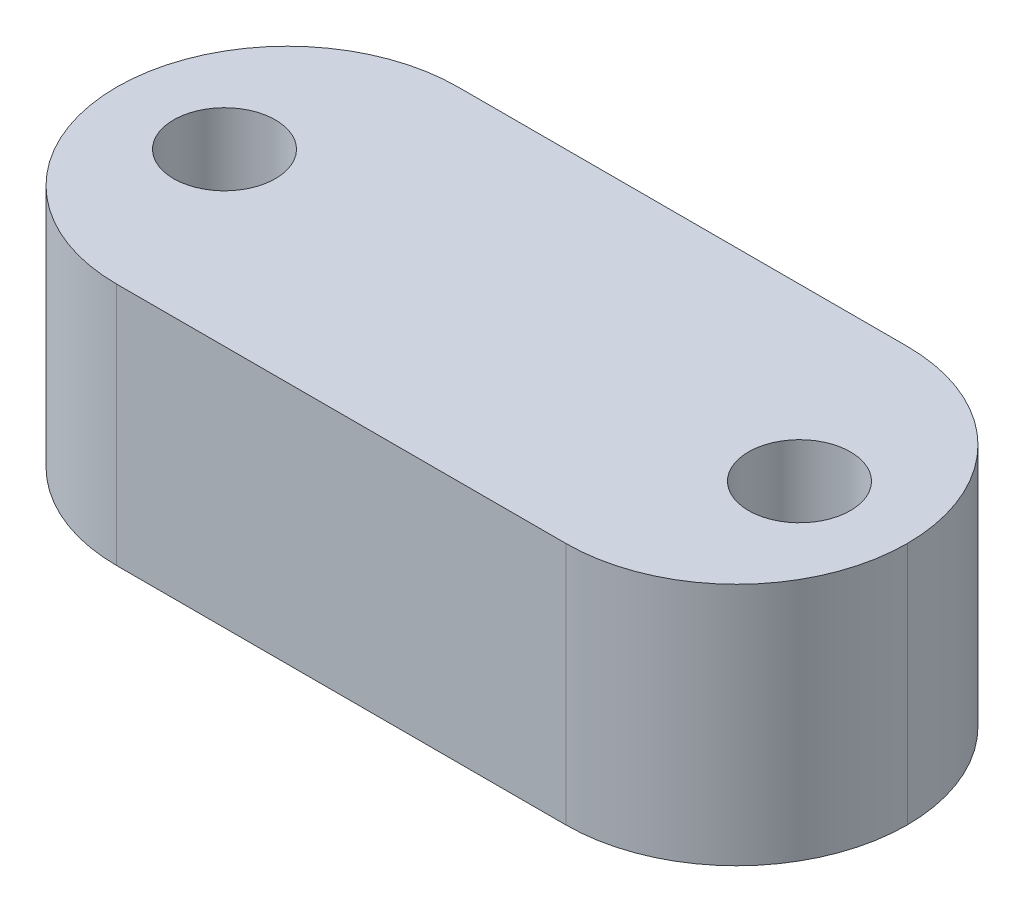
SolidWorks part; units mm, degrees
ref_plane "Front" through (0, 0, 0) normal (0, 0, 1) x (1, 0, 0)
ref_plane "Top" through (0, 0, 0) normal (0, 1, 0) x (1, 0, 0)
ref_plane "Right" through (0, 0, 0) normal (1, 0, 0) x (0, 0, -1)
sketch "Sketch1" plane through (0, 0, 0) normal (0, 1, 0) x (1, 0, 0)
  line L0 (0, 7.5406) -> (0, -7.5406) construction
  line L1 (-17.4625, 7.5406) -> (17.4625, 7.5406)
  line L2 (-17.4625, 7.5406) -> (-17.4625, -7.5406)
  line L3 (-17.4625, -7.5406) -> (17.4625, -7.5406)
  line L4 (17.4625, 7.5406) -> (17.4625, -7.5406)
  dimension "D1" = 15.0812
  dimension "D2" = 34.925
extrude "Extrude1" add sketch "Sketch1" along normal blind 10.7696
hole_wizard "M4 Clearance Hole1" positions "Sketch4" profile "Sketch3" hole size "M4" standard "Ansi Metric" end condition through all
sketch "Sketch4" plane through (0, 10.7696, 0) normal (0, 1, 0) x (-1, 0, 0)
  line L0 (12.7, 0) -> (-12.7, 0) construction
  point P0 (12.7, 0)
  point P1 (-12.7, 0)
  dimension "D1" = 25.4
sketch "Sketch3" plane through (-12.7, 10.7696, 0) normal (1, 0, 0) x (0, 0, 1)
  line L0 (0, 0) -> (0, 10.7696)
  line L1 (0, 10.7696) -> (2.25, 10.7696)
  line L2 (2.25, 10.7696) -> (2.25, 0)
  line L5 (2.25, 0) -> (0, 0)
  line L11 (0, -6.35) -> (0, 107.95) construction
  dimension "Thru Hole Dia." = 4.5
  dimension "Thru Hole Depth" = 10.7696
fillet "Fillet1" radius 7.5406 4 edges at (17.4625, 5.3848, 7.5406) (17.4625, 5.3848, -7.5406) (-17.4625, 5.3848, -7.5406) (-17.4625, 5.3848, 7.5406)
